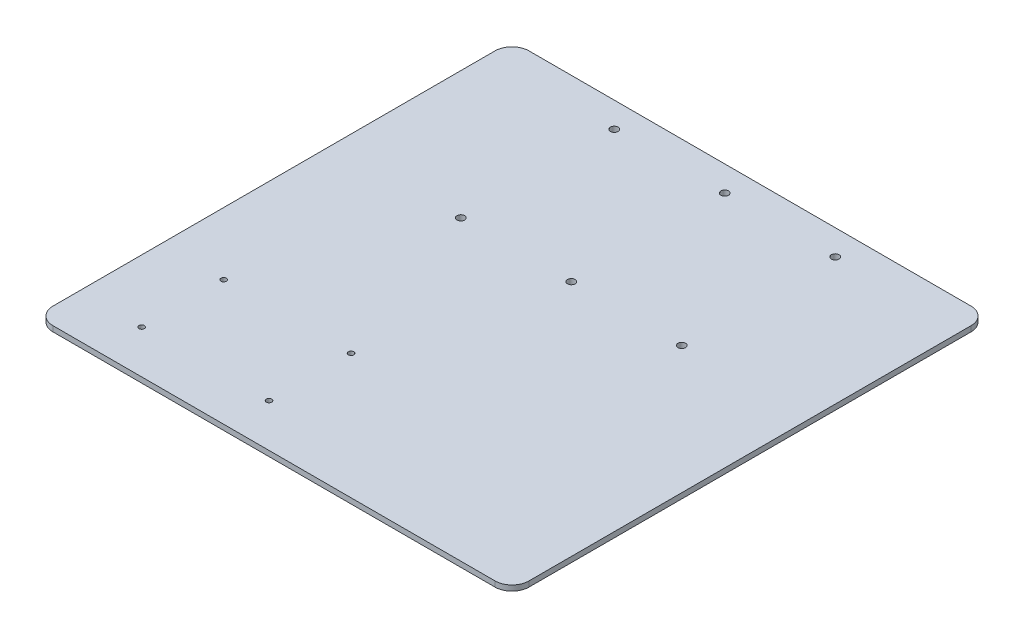
SolidWorks part; units mm, degrees
ref_plane "Front Plane" through (0, 0, 0) normal (0, 0, 1) x (1, 0, 0)
ref_plane "Top Plane" through (0, 0, 0) normal (0, 1, 0) x (1, 0, 0)
ref_plane "Right Plane" through (0, 0, 0) normal (1, 0, 0) x (0, 0, -1)
sketch "Sketch1" plane through (0, 0, 0) normal (0, 1, 0) x (1, 0, 0)
  line L1 (-140, 140) -> (140, 140)
  line L2 (-140, 140) -> (-140, -140)
  line L3 (-140, -140) -> (140, -140)
  line L4 (140, 140) -> (140, -140)
  line L5 (-140, 140) -> (140, -140) construction
  line L6 (-140, -140) -> (140, 140) construction
  point P0 (0, 0)
  dimension "D1" = 280
  dimension "D2" = 280
base flange "Base-Flange1" sketch "Sketch1" thickness 3.18 reverse thickness direction no parameters "D1"=3
sketch "Sketch6" plane through (0, 0, 0) normal (0, 1, 0) x (1, 0, 0)
  line L0 (-82.5, 121.25) -> (-47.5, 121.25) construction
  line L1 (-82.5, 129) -> (-47.5, 129)
  line L2 (-82.5, 129) -> (-82.5, 31)
  line L3 (-82.5, 31) -> (-47.5, 31)
  line L4 (-47.5, 129) -> (-47.5, 31)
  line L5 (-82.5, 129) -> (-47.5, 31) construction
  line L6 (-82.5, 31) -> (-47.5, 129) construction
  line L7 (-82.5, 38.75) -> (-47.5, 38.75) construction
  line L8 (-82.5, 38.75) -> (-47.5, 31) construction
  line L9 (-82.5, 31) -> (-47.5, 38.75) construction
  line L10 (-47.5, 44.2419) -> (-47.5, 129) construction
  line L11 (-82.5, 129) -> (-47.5, 121.25) construction
  line L12 (-47.5, 121.25) -> (-47.5, 129) construction
  line L13 (-82.5, 121.25) -> (-47.5, 129) construction
  line L14 (-17.5, 129) -> (-17.5, 31)
  line L15 (-17.5, 129) -> (17.5, 129)
  line L16 (17.5, 129) -> (17.5, 31)
  line L17 (-17.5, 31) -> (17.5, 31)
  line L18 (47.5, 129) -> (47.5, 31)
  line L19 (47.5, 129) -> (82.5, 129)
  line L20 (82.5, 129) -> (82.5, 31)
  line L21 (47.5, 31) -> (82.5, 31)
  line L22 (-117.25, -90.5) -> (-14.25, -90.5) construction
  line L23 (-100, 16) -> (100, 16)
  line L24 (-100, 16) -> (-100, -38)
  line L25 (-100, -38) -> (100, -38)
  line L26 (100, 16) -> (100, -38)
  line L27 (-100, 16) -> (100, -38) construction
  line L28 (-100, -38) -> (100, 16) construction
  line L29 (15.75, -53) -> (115.75, -53)
  line L30 (15.75, -53) -> (15.75, -128)
  line L31 (15.75, -128) -> (115.75, -128)
  line L32 (115.75, -53) -> (115.75, -128)
  line L33 (15.75, -53) -> (115.75, -128) construction
  line L34 (15.75, -128) -> (115.75, -53) construction
  line L35 (-117.25, -64) -> (-14.25, -64)
  line L36 (-117.25, -64) -> (-117.25, -117)
  line L37 (-117.25, -117) -> (-14.25, -117)
  line L38 (-14.25, -64) -> (-14.25, -117)
  line L39 (-117.25, -64) -> (-14.25, -117) construction
  line L40 (-117.25, -117) -> (-14.25, -64) construction
  line L41 (-103.215, -66.37) -> (-28.285, -66.37) construction
  line L42 (-103.215, -66.37) -> (-103.215, -114.63) construction
  line L43 (-103.215, -114.63) -> (-28.285, -114.63) construction
  line L44 (-28.285, -66.37) -> (-28.285, -114.63) construction
  line L45 (-103.215, -66.37) -> (-28.285, -114.63) construction
  line L46 (-103.215, -114.63) -> (-28.285, -66.37) construction
  line L47 (65.75, -90.5) -> (-65.75, -90.5) construction
  line L48 (-140, -140) -> (140, -140) construction
  circle A2 centre (-65, 125.125) radius 2.25
  circle A3 centre (-65, 34.875) radius 2.25
  circle A4 centre (0, 125.125) radius 2.25
  circle A5 centre (0, 34.875) radius 2.25
  circle A6 centre (65, 125.125) radius 2.25
  circle A7 centre (65, 34.875) radius 2.25
  circle A8 centre (-28.285, -114.63) radius 1.6
  circle A9 centre (-103.215, -114.63) radius 1.6
  circle A10 centre (-103.215, -66.37) radius 1.6
  circle A11 centre (-28.285, -66.37) radius 1.6
  point P0 (-65, 80)
  point P7 (0, -11)
  point P36 (65.75, -90.5)
  point P41 (-65.75, -90.5)
  point P47 (-65.75, -90.5)
  point P57 (0, -90.5)
  dimension "D5" = 4.5
  dimension "D6" = 4.5
  dimension "D17" = 3.2
  dimension "D18" = 3.2
  dimension "D1" = 35
  dimension "D2" = 98
  dimension "D3" = 82.5
  dimension "D4" = 41.25
  dimension "D8" = 54
  dimension "D9" = 75
  dimension "D10" = 100
  dimension "D11" = 53
  dimension "D12" = 103
  dimension "D13" = 15
  dimension "D14" = 15
  dimension "D15" = 48.26
  dimension "D16" = 74.93
  dimension "D19" = 200
  dimension "D20" = 30
  dimension "D21" = 12
  dimension "D7" = 3
extrude "Cut-Extrude1" cut sketch "Sketch6" against normal blind 10 contours A4 | A5 | A7 | A6 | A9 | A8 | A11 | A10 | A3 | A2
fillet "Fillet1" radius 10 4 edges at (-140, -1.59, 140) (140, -1.59, 140) (140, -1.59, -140) (-140, -1.59, -140)
sketch "Bend-Lines1" [suppressed] plane through (0, 0, 0) normal (0, 1, 0) x (1, 0, 0)
sketch "Bounding-Box1" [suppressed] plane through (0, 0, 0) normal (0, 1, 0) x (1, 0, 0)
sheet metal parameters "Sheet-Metal1" thickness 3.18 parameters "D1"=3
flat pattern "Flat-Pattern1" [suppressed]
sketch "Bend-Lines2" plane through (0, 0, 0) normal (0, 1, 0) x (1, 0, 0)
sketch3d "Bounding-Box2" [suppressed]
  line L0 (-150, 150, 0) -> (-150, -150, 0) construction
  line L1 (150, 150, 0) -> (150, -150, 0) construction
  line L2 (-150, 150, 0) -> (150, 150, 0) construction
  line L3 (-150, -150, 0) -> (150, -150, 0) construction
sheet metal parameters "Sheet-Metal2" thickness 3.18 parameters "D1"=3
flat pattern "Flat-Pattern1"
sketch "Bend-Lines2" plane through (0, 0, 0) normal (0, 1, 0) x (1, 0, 0)
sketch3d "Bounding-Box2" [suppressed]
  line L0 (-140, -140, 0) -> (140, -140, 0) construction
  line L1 (-140, 140, 0) -> (140, 140, 0) construction
  line L2 (-140, -140, 0) -> (-140, 140, 0) construction
  line L3 (140, -140, 0) -> (140, 140, 0) construction
